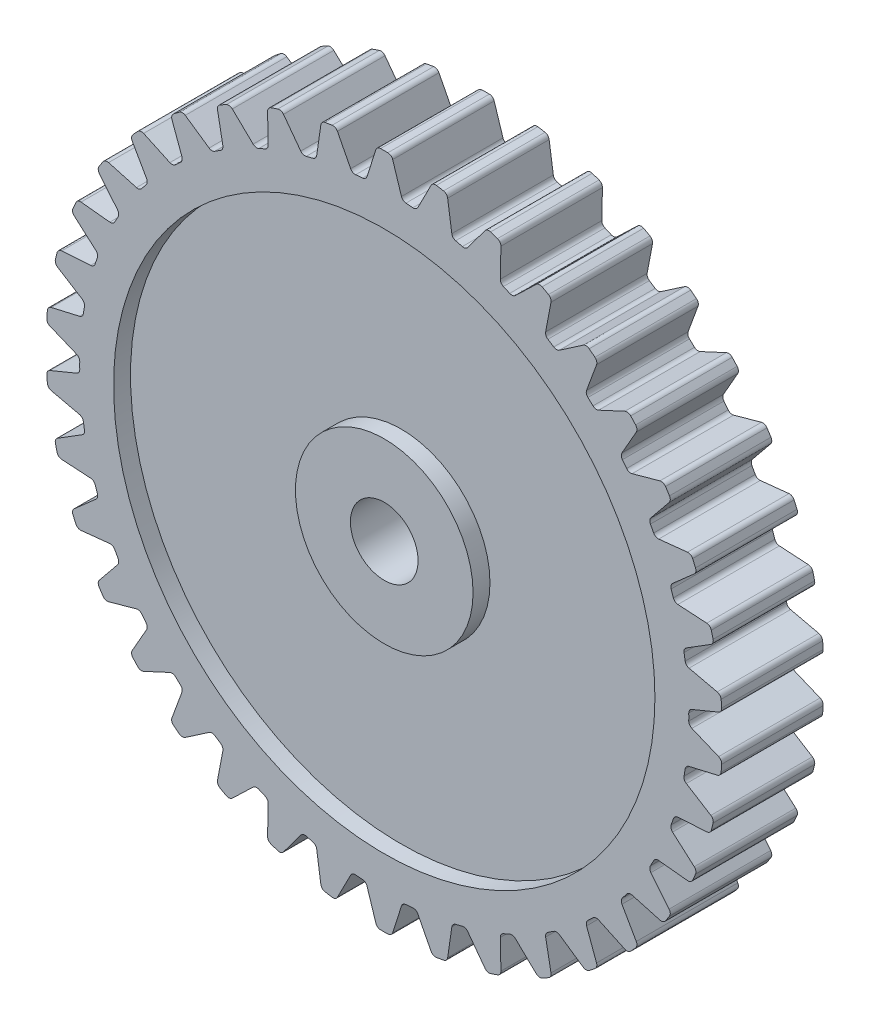
SolidWorks part; units mm, degrees
ref_plane "Front Plane" through (0, 0, 0) normal (0, 0, 1) x (1, 0, 0)
ref_plane "Top Plane" through (0, 0, 0) normal (0, 1, 0) x (1, 0, 0)
ref_plane "Right Plane" through (0, 0, 0) normal (1, 0, 0) x (0, 0, -1)
sketch "Sketch1" plane through (0, 0, 0) normal (0, 0, 1) x (1, 0, 0)
  circle A2 centre (0, 0) radius 18
  dimension "Blank diameter" = 36
extrude "Body" add sketch "Sketch1" against normal blind 6
sketch "Sketch2" plane through (0, 0, 0) normal (0, 0, 1) x (1, 0, 0)
  line L0 (0, 34.3446) -> (0, 3.6554) construction
  line L1 (-0.755, 18.985) -> (-1.0801, 17.9676)
  line L2 (-0.755, 18.985) -> (-0.4321, 19.9953)
  line L3 (0.755, 18.985) -> (1.0801, 17.9676)
  line L4 (0.755, 18.985) -> (0.4321, 19.9953)
  line L5 (0, 0) -> (-1.7569, 44.1774) construction
  line L6 (0, 0) -> (1.6969, 42.6688) construction
  arc A0 (0.4321, 19.9953) -> (-0.4321, 19.9953) centre (0, 0) ccw
  arc A1 (0.755, 18.985) -> (-0.755, 18.985) centre (0, 0) ccw construction
  arc A2 (1.0801, 17.9676) -> (-1.0801, 17.9676) centre (0, 0) ccw
  point P1 (0, 19)
  dimension "D2" = 20
  dimension "D3" = 20
  dimension "Full diameter" = 40
  dimension "Pitch diameter" = 38
  dimension "Blank diameter" = 36
  dimension "Tooth width PCD" = 1.51
extrude "Tooth" add sketch "Sketch2" against normal blind 6
fillet "Tooth Fillet" radius 0.3 4 edges at (-0.4321, 19.9953, -3) (-1.0801, 17.9676, -3) (0.4321, 19.9953, -3) (1.0801, 17.9676, -3)
pattern_circular "Tooth Pattern" count 38 over 360 about axis through (0, 0, 0) along (0, 0, 1) of "Tooth", "Tooth Fillet"
ref_axis "Axis1" through (0, 0, 0) along (0, 0, -1)
sketch "Sketch3" plane through (0, 0, 0) normal (0, 0, 1) x (1, 0, 0)
  circle A0 centre (0, 0) radius 5.25
  circle A1 centre (0, 0) radius 16
  dimension "Plastic boss" = 10.5
  dimension "Resses" = 32
extrude "Resses1" cut sketch "Sketch3" against normal blind 1
sketch "Sketch4" plane through (0, 0, -6) normal (0, 0, -1) x (-1, 0, 0)
  circle A0 centre (0, 0) radius 16
  circle A1 centre (0, 0) radius 5.25
  dimension "Plastic boss" = 10.5
  dimension "Resses" = 32
extrude "Resses2" cut sketch "Sketch4" against normal blind 1
sketch "Sketch5" plane through (0, 0, -6) normal (0, 0, -1) x (-1, 0, 0)
  circle A0 centre (0, 0) radius 5
  dimension "D1" = 10
extrude "Brass boss" add sketch "Sketch5" along normal blind 5.7
sketch "Sketch6" plane through (0, 0, -11.7) normal (0, 0, -1) x (-1, 0, 0)
  circle A0 centre (0, 0) radius 2
  dimension "D1" = 4
extrude "Bore" cut sketch "Sketch6" against normal through all
sketch "Sketch7" plane through (0, 0, 0) normal (0, 1, 0) x (1, 0, 0)
  circle A0 centre (0, 8.8626) radius 1
  dimension "D1" = 2
extrude "Grub screw" cut sketch "Sketch7" against normal through all
sketch "Sketch8" plane through (0, 0, -5) normal (0, 0, -1) x (-1, 0, 0)
  circle A0 centre (-0.8321, 10.5608) radius 1.8434
extrude "Extrude1" [suppressed] add sketch "Sketch8" along normal blind 5
